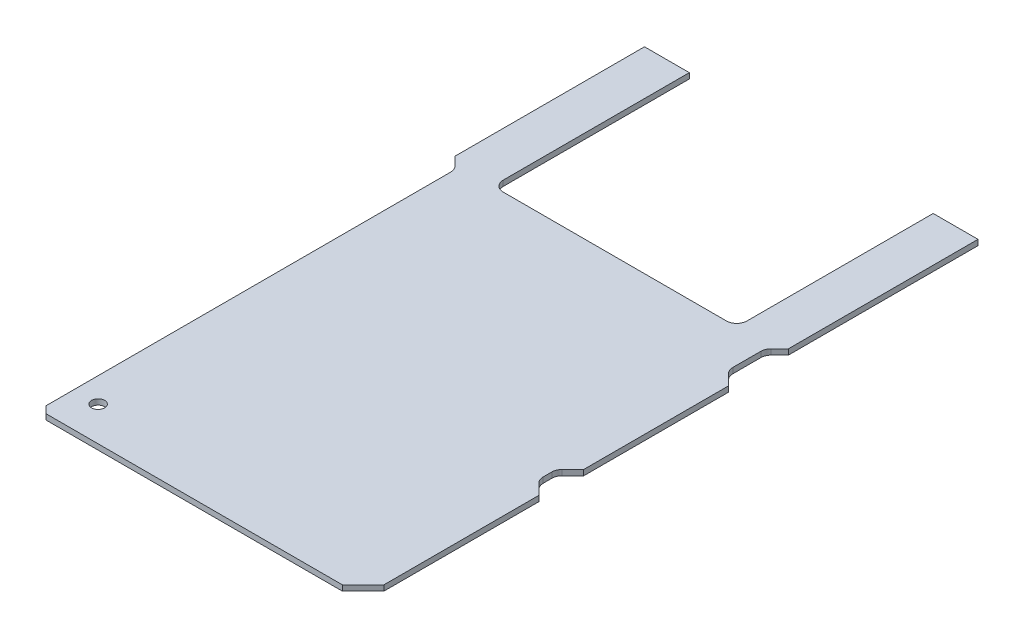
SolidWorks part; units mm, degrees
ref_plane "Front Plane" through (0, 0, 0) normal (0, 0, 1) x (1, 0, 0)
ref_plane "Top Plane" through (0, 0, 0) normal (0, 1, 0) x (1, 0, 0)
ref_plane "Right Plane" through (0, 0, 0) normal (1, 0, 0) x (0, 0, -1)
sketch "Sketch1" plane through (0, 0, 0) normal (0, 1, 0) x (1, 0, 0)
  line L1 (45, -88.5) -> (-45, -88.5)
  line L2 (45, -88.5) -> (45, 88.5)
  line L3 (45, 88.5) -> (-45, 88.5)
  line L4 (-45, -88.5) -> (-45, 88.5)
  line L5 (45, -88.5) -> (-45, 88.5) construction
  line L6 (45, 88.5) -> (-45, -88.5) construction
  point P0 (0, 0)
  dimension "D1" = 90
  dimension "D2" = 177
extrude "Boss-Extrude1" add sketch "Sketch1" along normal blind 1.6
sketch "Sketch5" plane through (0, 0, 0) normal (0, -1, 0) x (1, 0, 0)
  line L0 (45, 88.5) -> (45, -88.5) construction
  line L1 (37.6, -44) -> (37.6, -48)
  line L2 (37.6, -44) -> (22.4, -44)
  line L3 (22.4, -44) -> (22.4, -48)
  line L4 (37.6, -48) -> (22.4, -48)
  line L5 (16.1, -44) -> (16.1, -48)
  line L6 (16.1, -44) -> (0.9, -44)
  line L7 (0.9, -44) -> (0.9, -48)
  line L8 (16.1, -48) -> (0.9, -48)
  line L9 (37.6, -80) -> (37.6, -84)
  line L10 (37.6, -80) -> (22.4, -80)
  line L11 (22.4, -80) -> (22.4, -84)
  line L12 (37.6, -84) -> (22.4, -84)
  line L13 (12.1, -80) -> (12.1, -84)
  line L14 (12.1, -80) -> (-3.1, -80)
  line L15 (-3.1, -80) -> (-3.1, -84)
  line L16 (12.1, -84) -> (-3.1, -84)
  line L17 (2.025, -44.54) -> (14.975, -44.54)
  line L18 (2.025, -44.54) -> (2.025, -47.46)
  line L19 (2.025, -47.46) -> (14.975, -47.46)
  line L20 (14.975, -44.54) -> (14.975, -47.46)
  line L21 (23.525, -44.54) -> (36.475, -44.54)
  line L22 (23.525, -44.54) -> (23.525, -47.46)
  line L23 (23.525, -47.46) -> (36.475, -47.46)
  line L24 (36.475, -44.54) -> (36.475, -47.46)
  line L25 (-1.975, -80.54) -> (10.975, -80.54)
  line L26 (-1.975, -80.54) -> (-1.975, -83.46)
  line L27 (-1.975, -83.46) -> (10.975, -83.46)
  line L28 (10.975, -80.54) -> (10.975, -83.46)
  line L29 (23.525, -80.54) -> (36.475, -80.54)
  line L30 (23.525, -80.54) -> (23.525, -83.46)
  line L31 (23.525, -83.46) -> (36.475, -83.46)
  line L32 (36.475, -80.54) -> (36.475, -83.46)
  line L33 (-22, -41.5) -> (43, -41.5) construction
  line L34 (-22, -41.5) -> (-22, -86.5) construction
  line L35 (-22, -86.5) -> (43, -86.5) construction
  line L36 (43, -41.5) -> (43, -86.5) construction
  line L37 (45, -88.5) -> (-45, -88.5) construction
  point P16 (8.5, -44)
  point P17 (30, -44)
  point P18 (4.5, -84)
  point P19 (30, -84)
  point P25 (37.6, -82)
  point P26 (37.6, -46)
  point P38 (8.5, -44.54)
  point P39 (2.025, -46)
  point P40 (0.9, -46)
  point P41 (30, -44.54)
  point P42 (-1.975, -82)
  point P43 (-3.1, -82)
  point P44 (4.5, -83.46)
  point P45 (30, -83.46)
  dimension "D1" = 15.2
  dimension "D2" = 4
  dimension "D3" = 21.5
  dimension "D4" = 25.5
  dimension "D5" = 2.92
  dimension "D6" = 12.95
  dimension "D7" = 36
  dimension "D8" = 65
  dimension "D9" = 45
  dimension "D10" = 2.5
  dimension "D11" = 5.4
  dimension "D12" = 2
  dimension "D13" = 2
sketch "Sketch7" plane through (0, 0, 0) normal (0, -1, 0) x (1, 0, 0)
  line L0 (-45, -30.1257) -> (-48.3743, -33.5)
  line L1 (-45, -88.5) -> (-48.3743, -88.5)
  line L2 (-45, -88.5) -> (-45, -30.1257)
  line L4 (-48.3743, -88.5) -> (-48.3743, -33.5)
  line L5 (45, -88.5) -> (48.3743, -88.5)
  line L6 (45, -88.5) -> (45, -30.1257)
  line L8 (48.3743, -88.5) -> (48.3743, -33.5)
  line L9 (45, -30.1257) -> (48.3743, -33.5)
  line M9 (-45, 88.5) -> (-45, -88.5)
  line M11 (45, -88.5) -> (45, 88.5)
  dimension "D1" = 3.3743
  dimension "D2" = 55
  dimension "D3" = 45
extrude "Boss-Extrude4" add sketch "Sketch7" against normal up to surface (1.6 mm away) contours L4 L1 L0 M9 | L9 L5 L8 M11 region at (-46.6704, 0, -60.1481) region at (46.6704, 0, -60.1481) up to face at (0, 1.6, 0)
sketch "Sketch8" plane through (0, 1.6, 0) normal (0, 1, 0) x (1, 0, 0)
  line L0 (-30.48, 25.5) -> (30.48, 25.5) construction
  line L2 (48.3743, 88.5) -> (-48.3743, 88.5) construction
  line L3 (31.0783, -41.8002) -> (31.0783, -43.6252) construction
  line L4 (31.0783, -43.6252) -> (29.8783, -43.6252) construction
  line L5 (31.0783, -79.9002) -> (31.0783, -81.7252) construction
  line L6 (31.0783, -81.7252) -> (29.8783, -81.7252) construction
  line L7 (6.9977, -30.7614) -> (6.9977, -16.766)
  line L8 (6.9977, -16.766) -> (-6.9977, -16.766)
  line L9 (-6.9977, -16.766) -> (-6.9977, -30.7614)
  line L10 (-6.9977, -30.7614) -> (6.9977, -30.7614)
  line L11 (6.9977, -30.7614) -> (6.9977, -16.766)
  line L12 (6.9977, -16.766) -> (-6.9977, -16.766)
  line L13 (-6.9977, -16.766) -> (-6.9977, -30.7614)
  line L14 (-6.9977, -30.7614) -> (6.9977, -30.7614)
  line L15 (-11.9253, -30.7614) -> (-11.9253, -16.766)
  line L16 (-11.9253, -16.766) -> (-25.9207, -16.766)
  line L17 (-25.9207, -16.766) -> (-25.9207, -30.7614)
  line L18 (-25.9207, -30.7614) -> (-11.9253, -30.7614)
  line L19 (-11.9253, -30.7614) -> (-11.9253, -16.766)
  line L20 (-11.9253, -16.766) -> (-25.9207, -16.766)
  line L21 (-25.9207, -16.766) -> (-25.9207, -30.7614)
  line L22 (-25.9207, -30.7614) -> (-11.9253, -30.7614)
  line L23 (44.8437, -11.8384) -> (44.8437, 2.157)
  line L24 (44.8437, 2.157) -> (30.8483, 2.157)
  line L25 (30.8483, 2.157) -> (30.8483, -11.8384)
  line L26 (30.8483, -11.8384) -> (44.8437, -11.8384)
  line L27 (44.8437, -11.8384) -> (44.8437, 2.157)
  line L28 (44.8437, 2.157) -> (30.8483, 2.157)
  line L29 (30.8483, 2.157) -> (30.8483, -11.8384)
  line L30 (30.8483, -11.8384) -> (44.8437, -11.8384)
  line L31 (6.9977, -49.6844) -> (6.9977, -35.689)
  line L32 (6.9977, -35.689) -> (-6.9977, -35.689)
  line L33 (-6.9977, -35.689) -> (-6.9977, -49.6844)
  line L34 (-6.9977, -49.6844) -> (6.9977, -49.6844)
  line L35 (6.9977, -49.6844) -> (6.9977, -35.689)
  line L36 (6.9977, -35.689) -> (-6.9977, -35.689)
  line L37 (-6.9977, -35.689) -> (-6.9977, -49.6844)
  line L38 (-6.9977, -49.6844) -> (6.9977, -49.6844)
  line L39 (-11.9253, -49.6844) -> (-11.9253, -35.689)
  line L40 (-11.9253, -35.689) -> (-25.9207, -35.689)
  line L41 (-25.9207, -35.689) -> (-25.9207, -49.6844)
  line L42 (-25.9207, -49.6844) -> (-11.9253, -49.6844)
  line L43 (-11.9253, -49.6844) -> (-11.9253, -35.689)
  line L44 (-11.9253, -35.689) -> (-25.9207, -35.689)
  line L45 (-25.9207, -35.689) -> (-25.9207, -49.6844)
  line L46 (-25.9207, -49.6844) -> (-11.9253, -49.6844)
  line L47 (25.9207, -30.7614) -> (25.9207, -16.766)
  line L48 (25.9207, -16.766) -> (11.9253, -16.766)
  line L49 (11.9253, -16.766) -> (11.9253, -30.7614)
  line L50 (11.9253, -30.7614) -> (25.9207, -30.7614)
  line L51 (25.9207, -30.7614) -> (25.9207, -16.766)
  line L52 (25.9207, -16.766) -> (11.9253, -16.766)
  line L53 (11.9253, -16.766) -> (11.9253, -30.7614)
  line L54 (11.9253, -30.7614) -> (25.9207, -30.7614)
  line L55 (6.9977, -68.6074) -> (6.9977, -54.612)
  line L56 (6.9977, -54.612) -> (-6.9977, -54.612)
  line L57 (-6.9977, -54.612) -> (-6.9977, -68.6074)
  line L58 (-6.9977, -68.6074) -> (6.9977, -68.6074)
  line L59 (6.9977, -68.6074) -> (6.9977, -54.612)
  line L60 (6.9977, -54.612) -> (-6.9977, -54.612)
  line L61 (-6.9977, -54.612) -> (-6.9977, -68.6074)
  line L62 (-6.9977, -68.6074) -> (6.9977, -68.6074)
  line L63 (-11.9253, -68.6074) -> (-11.9253, -54.612)
  line L64 (-11.9253, -54.612) -> (-25.9207, -54.612)
  line L65 (-25.9207, -54.612) -> (-25.9207, -68.6074)
  line L66 (-25.9207, -68.6074) -> (-11.9253, -68.6074)
  line L67 (-11.9253, -68.6074) -> (-11.9253, -54.612)
  line L68 (-11.9253, -54.612) -> (-25.9207, -54.612)
  line L69 (-25.9207, -54.612) -> (-25.9207, -68.6074)
  line L70 (-25.9207, -68.6074) -> (-11.9253, -68.6074)
  line L71 (25.9207, -49.6844) -> (25.9207, -35.689)
  line L72 (25.9207, -35.689) -> (11.9253, -35.689)
  line L73 (11.9253, -35.689) -> (11.9253, -49.6844)
  line L74 (11.9253, -49.6844) -> (25.9207, -49.6844)
  line L75 (25.9207, -49.6844) -> (25.9207, -35.689)
  line L76 (25.9207, -35.689) -> (11.9253, -35.689)
  line L77 (11.9253, -35.689) -> (11.9253, -49.6844)
  line L78 (11.9253, -49.6844) -> (25.9207, -49.6844)
  line L79 (25.9207, -68.6074) -> (25.9207, -54.612)
  line L80 (25.9207, -54.612) -> (11.9253, -54.612)
  line L81 (11.9253, -54.612) -> (11.9253, -68.6074)
  line L82 (11.9253, -68.6074) -> (25.9207, -68.6074)
  line L83 (25.9207, -68.6074) -> (25.9207, -54.612)
  line L84 (25.9207, -54.612) -> (11.9253, -54.612)
  line L85 (11.9253, -54.612) -> (11.9253, -68.6074)
  line L86 (11.9253, -68.6074) -> (25.9207, -68.6074)
  line L87 (-30.8483, -30.7614) -> (-30.8483, -16.766)
  line L88 (-30.8483, -16.766) -> (-44.8437, -16.766)
  line L89 (-44.8437, -16.766) -> (-44.8437, -30.7614)
  line L90 (-44.8437, -30.7614) -> (-30.8483, -30.7614)
  line L91 (-30.8483, -30.7614) -> (-30.8483, -16.766)
  line L92 (-30.8483, -16.766) -> (-44.8437, -16.766)
  line L93 (-44.8437, -16.766) -> (-44.8437, -30.7614)
  line L94 (-44.8437, -30.7614) -> (-30.8483, -30.7614)
  line L95 (-30.8483, -11.8384) -> (-30.8483, 2.157)
  line L96 (-30.8483, 2.157) -> (-44.8437, 2.157)
  line L97 (-44.8437, 2.157) -> (-44.8437, -11.8384)
  line L98 (-44.8437, -11.8384) -> (-30.8483, -11.8384)
  line L99 (-30.8483, -11.8384) -> (-30.8483, 2.157)
  line L100 (-30.8483, 2.157) -> (-44.8437, 2.157)
  line L101 (-44.8437, 2.157) -> (-44.8437, -11.8384)
  line L102 (-44.8437, -11.8384) -> (-30.8483, -11.8384)
  line L103 (25.9207, -87.5304) -> (25.9207, -73.535)
  line L104 (25.9207, -73.535) -> (11.9253, -73.535)
  line L105 (11.9253, -73.535) -> (11.9253, -87.5304)
  line L106 (11.9253, -87.5304) -> (25.9207, -87.5304)
  line L107 (25.9207, -87.5304) -> (25.9207, -73.535)
  line L108 (25.9207, -73.535) -> (11.9253, -73.535)
  line L109 (11.9253, -73.535) -> (11.9253, -87.5304)
  line L110 (11.9253, -87.5304) -> (25.9207, -87.5304)
  line L111 (-30.8483, -87.5304) -> (-30.8483, -73.535)
  line L112 (-30.8483, -73.535) -> (-44.8437, -73.535)
  line L113 (-44.8437, -73.535) -> (-44.8437, -87.5304)
  line L114 (-44.8437, -87.5304) -> (-30.8483, -87.5304)
  line L115 (-30.8483, -87.5304) -> (-30.8483, -73.535)
  line L116 (-30.8483, -73.535) -> (-44.8437, -73.535)
  line L117 (-44.8437, -73.535) -> (-44.8437, -87.5304)
  line L118 (-44.8437, -87.5304) -> (-30.8483, -87.5304)
  line L119 (-30.8483, -68.6074) -> (-30.8483, -54.612)
  line L120 (-30.8483, -54.612) -> (-44.8437, -54.612)
  line L121 (-44.8437, -54.612) -> (-44.8437, -68.6074)
  line L122 (-44.8437, -68.6074) -> (-30.8483, -68.6074)
  line L123 (-30.8483, -68.6074) -> (-30.8483, -54.612)
  line L124 (-30.8483, -54.612) -> (-44.8437, -54.612)
  line L125 (-44.8437, -54.612) -> (-44.8437, -68.6074)
  line L126 (-44.8437, -68.6074) -> (-30.8483, -68.6074)
  line L127 (-30.8483, -49.6844) -> (-30.8483, -35.689)
  line L128 (-30.8483, -35.689) -> (-44.8437, -35.689)
  line L129 (-44.8437, -35.689) -> (-44.8437, -49.6844)
  line L130 (-44.8437, -49.6844) -> (-30.8483, -49.6844)
  line L131 (-30.8483, -49.6844) -> (-30.8483, -35.689)
  line L132 (-30.8483, -35.689) -> (-44.8437, -35.689)
  line L133 (-44.8437, -35.689) -> (-44.8437, -49.6844)
  line L134 (-44.8437, -49.6844) -> (-30.8483, -49.6844)
  line L135 (45.0596, 90.786) -> (-45.0596, 90.786)
  line L136 (-45.0596, 90.786) -> (-45.0596, 30.08)
  line L137 (-45.0596, 30.08) -> (45.0596, 30.08)
  line L138 (45.0596, 30.08) -> (45.0596, 90.786)
  line L139 (45.0596, 90.786) -> (-45.0596, 90.786)
  line L140 (-45.0596, 90.786) -> (-45.0596, 30.08)
  line L141 (-45.0596, 30.08) -> (45.0596, 30.08)
  line L142 (45.0596, 30.08) -> (45.0596, 90.786)
  line L143 (52.5, 98.836) -> (-52.5, 98.836)
  line L144 (52.5, -93.5094) -> (52.5, 98.836)
  line L145 (-52.5, -93.5094) -> (52.5, -93.5094)
  line L146 (-52.5, 98.836) -> (-52.5, -93.5094)
  line L147 (52.5, 98.836) -> (-52.5, 98.836)
  line L148 (52.5, -93.5094) -> (52.5, 98.836)
  line L149 (-52.5, -93.5094) -> (52.5, -93.5094)
  line L150 (-52.5, 98.836) -> (-52.5, -93.5094)
  line L151 (-18.0365, -73.765) -> (-19.8615, -73.765) construction
  line L152 (-19.8615, -73.765) -> (-19.8615, -72.565) construction
  line L153 (31.8783, -41.8002) -> (31.0783, -41.8002) construction
  line L154 (31.8783, -79.9002) -> (31.0783, -79.9002) construction
  line L155 (-18.0365, -74.565) -> (-18.0365, -73.765) construction
  line L156 (31.8783, -40.2252) -> (31.8783, -41.8002) construction
  line L157 (31.8783, -78.3252) -> (31.8783, -79.9002) construction
  line L158 (-16.4615, -74.565) -> (-18.0365, -74.565) construction
  line L159 (-6.9977, 7.0846) -> (-6.9977, 21.08) construction
  line L160 (6.9977, 21.08) -> (-6.9977, 21.08) construction
  line L161 (31.0783, -48.4502) -> (37.3483, -48.4502) construction
  line L162 (37.3483, -48.4502) -> (40.1483, -48.4502) construction
  line L163 (31.0783, -86.5502) -> (37.3483, -86.5502) construction
  line L164 (37.3483, -86.5502) -> (40.1483, -86.5502) construction
  line L165 (-24.6865, -73.765) -> (-24.6865, -80.035) construction
  line L166 (-24.6865, -80.035) -> (-24.6865, -82.835) construction
  line L167 (6.9977, 7.0846) -> (-6.9977, 7.0846) construction
  line L168 (43.3783, -48.4502) -> (43.3783, -41.8002) construction
  line L169 (43.3783, -41.8002) -> (42.5783, -41.8002) construction
  line L170 (43.3783, -86.5502) -> (43.3783, -79.9002) construction
  line L171 (43.3783, -79.9002) -> (42.5783, -79.9002) construction
  line L172 (-24.6865, -86.065) -> (-18.0365, -86.065) construction
  line L173 (-18.0365, -86.065) -> (-18.0365, -85.265) construction
  line L174 (6.9977, 7.0846) -> (6.9977, 21.08) construction
  line L175 (40.1483, -48.4502) -> (43.3783, -48.4502) construction
  line L176 (40.1483, -86.5502) -> (43.3783, -86.5502) construction
  line L177 (-24.6865, -82.835) -> (-24.6865, -86.065) construction
  line L178 (-25.9207, 7.0846) -> (-25.9207, 21.08) construction
  line L179 (-11.9253, 21.08) -> (-25.9207, 21.08) construction
  line L180 (29.8783, -43.6252) -> (29.8783, -46.6252) construction
  line L181 (29.8783, -81.7252) -> (29.8783, -84.7252) construction
  line L182 (-19.8615, -72.565) -> (-22.8615, -72.565) construction
  line L183 (-11.9253, 7.0846) -> (-25.9207, 7.0846) construction
  line L184 (31.0783, -46.6252) -> (31.0783, -48.4502) construction
  line L185 (31.0783, -84.7252) -> (31.0783, -86.5502) construction
  line L186 (-22.8615, -73.765) -> (-24.6865, -73.765) construction
  line L187 (-30.8483, 7.0846) -> (-44.8437, 7.0846) construction
  line L188 (-30.8483, 7.0846) -> (-30.8483, 21.08) construction
  line L189 (-30.8483, 21.08) -> (-44.8437, 21.08) construction
  line L190 (-44.8437, 7.0846) -> (-44.8437, 21.08) construction
  line L191 (30.8483, -26.2252) -> (30.8483, -40.2252) construction
  line L192 (30.8483, -40.2252) -> (31.8783, -40.2252) construction
  line L193 (30.8483, -64.3252) -> (30.8483, -78.3252) construction
  line L194 (30.8483, -78.3252) -> (31.8783, -78.3252) construction
  line L195 (-2.4615, -73.535) -> (-16.4615, -73.535) construction
  line L196 (-16.4615, -73.535) -> (-16.4615, -74.565) construction
  line L197 (-11.9253, 7.0846) -> (-11.9253, 21.08) construction
  line L198 (29.8783, -46.6252) -> (31.0783, -46.6252) construction
  line L199 (29.8783, -84.7252) -> (31.0783, -84.7252) construction
  line L200 (-22.8615, -72.565) -> (-22.8615, -73.765) construction
  line L201 (-6.9977, -11.8384) -> (-6.9977, 2.157) construction
  line L202 (6.9977, 2.157) -> (-6.9977, 2.157) construction
  line L203 (31.0783, -19.8252) -> (31.0783, -18.0002) construction
  line L204 (29.8783, -19.8252) -> (31.0783, -19.8252) construction
  line L205 (31.0783, -57.9252) -> (31.0783, -56.1002) construction
  line L206 (29.8783, -57.9252) -> (31.0783, -57.9252) construction
  line L207 (3.9385, -73.765) -> (5.7635, -73.765) construction
  line L208 (3.9385, -72.565) -> (3.9385, -73.765) construction
  line L209 (6.9977, -11.8384) -> (-6.9977, -11.8384) construction
  line L210 (31.0783, -22.8252) -> (29.8783, -22.8252) construction
  line L211 (31.0783, -24.6502) -> (31.0783, -22.8252) construction
  line L212 (31.0783, -60.9252) -> (29.8783, -60.9252) construction
  line L213 (31.0783, -62.7502) -> (31.0783, -60.9252) construction
  line L214 (0.9385, -73.765) -> (0.9385, -72.565) construction
  line L215 (-0.8865, -73.765) -> (0.9385, -73.765) construction
  line L216 (6.9977, -11.8384) -> (6.9977, 2.157) construction
  line L217 (29.8783, -22.8252) -> (29.8783, -19.8252) construction
  line L218 (29.8783, -60.9252) -> (29.8783, -57.9252) construction
  line L219 (0.9385, -72.565) -> (3.9385, -72.565) construction
  line L220 (-25.9207, -11.8384) -> (-25.9207, 2.157) construction
  line L221 (-11.9253, 2.157) -> (-25.9207, 2.157) construction
  line L222 (43.3783, -18.0002) -> (43.3783, -24.6502) construction
  line L223 (40.1483, -18.0002) -> (43.3783, -18.0002) construction
  line L224 (43.3783, -56.1002) -> (43.3783, -62.7502) construction
  line L225 (40.1483, -56.1002) -> (43.3783, -56.1002) construction
  line L226 (5.7635, -86.065) -> (-0.8865, -86.065) construction
  line L227 (5.7635, -82.835) -> (5.7635, -86.065) construction
  line L228 (-11.9253, -11.8384) -> (-25.9207, -11.8384) construction
  line L229 (31.0783, -18.0002) -> (37.3483, -18.0002) construction
  line L230 (31.0783, -56.1002) -> (37.3483, -56.1002) construction
  line L231 (5.7635, -73.765) -> (5.7635, -80.035) construction
  line L232 (-11.9253, -11.8384) -> (-11.9253, 2.157) construction
  line L233 (37.3483, -18.0002) -> (40.1483, -18.0002) construction
  line L234 (37.3483, -56.1002) -> (40.1483, -56.1002) construction
  line L235 (5.7635, -80.035) -> (5.7635, -82.835) construction
  line L236 (30.8483, 7.0846) -> (30.8483, 21.08) construction
  line L237 (44.8437, 21.08) -> (30.8483, 21.08) construction
  line L238 (44.8483, -40.2252) -> (44.8483, -26.2252) construction
  line L239 (42.5783, -26.2252) -> (44.8483, -26.2252) construction
  line L240 (44.8483, -78.3252) -> (44.8483, -64.3252) construction
  line L241 (42.5783, -64.3252) -> (44.8483, -64.3252) construction
  line L242 (-16.4615, -87.535) -> (-2.4615, -87.535) construction
  line L243 (-2.4615, -85.265) -> (-2.4615, -87.535) construction
  line L244 (44.8437, 7.0846) -> (30.8483, 7.0846) construction
  line L245 (43.3783, -24.6502) -> (42.5783, -24.6502) construction
  line L246 (43.3783, -62.7502) -> (42.5783, -62.7502) construction
  line L247 (-0.8865, -86.065) -> (-0.8865, -85.265) construction
  line L248 (44.8437, 7.0846) -> (44.8437, 21.08) construction
  line L249 (42.5783, -24.6502) -> (42.5783, -26.2252) construction
  line L250 (42.5783, -62.7502) -> (42.5783, -64.3252) construction
  line L251 (-0.8865, -85.265) -> (-2.4615, -85.265) construction
  line L252 (25.9207, 7.0846) -> (11.9253, 7.0846) construction
  line L253 (11.9253, 7.0846) -> (11.9253, 21.08) construction
  line L254 (25.9207, 21.08) -> (11.9253, 21.08) construction
  line L255 (42.5783, -41.8002) -> (42.5783, -40.2252) construction
  line L256 (42.5783, -79.9002) -> (42.5783, -78.3252) construction
  line L257 (-18.0365, -85.265) -> (-16.4615, -85.265) construction
  line L258 (25.9207, 7.0846) -> (25.9207, 21.08) construction
  line L259 (42.5783, -40.2252) -> (44.8483, -40.2252) construction
  line L260 (42.5783, -78.3252) -> (44.8483, -78.3252) construction
  line L261 (-16.4615, -85.265) -> (-16.4615, -87.535) construction
  line L262 (11.9253, -11.8384) -> (11.9253, 2.157) construction
  line L263 (25.9207, 2.157) -> (11.9253, 2.157) construction
  line L264 (31.8783, -24.6502) -> (31.0783, -24.6502) construction
  line L265 (31.8783, -62.7502) -> (31.0783, -62.7502) construction
  line L266 (-0.8865, -74.565) -> (-0.8865, -73.765) construction
  line L267 (25.9207, -11.8384) -> (11.9253, -11.8384) construction
  line L268 (30.8483, -26.2252) -> (31.8783, -26.2252) construction
  line L269 (30.8483, -64.3252) -> (31.8783, -64.3252) construction
  line L270 (-2.4615, -73.535) -> (-2.4615, -74.565) construction
  line L271 (25.9207, -11.8384) -> (25.9207, 2.157) construction
  line L272 (31.8783, -26.2252) -> (31.8783, -24.6502) construction
  line L273 (31.8783, -64.3252) -> (31.8783, -62.7502) construction
  line L274 (-2.4615, -74.565) -> (-0.8865, -74.565) construction
  line L275 (-24.6865, -86.065) -> (-25.1945, -86.065) construction
  line L276 (-25.1945, -86.065) -> (-25.1945, -73.765) construction
  line L277 (-25.1945, -73.765) -> (-24.6865, -73.765) construction
  line L278 (31.0783, -48.4502) -> (31.0783, -48.9582) construction
  line L279 (31.0783, -48.9582) -> (43.3783, -48.9582) construction
  line L280 (43.3783, -48.9582) -> (43.3783, -48.4502) construction
  line L281 (31.0783, -56.1002) -> (31.0783, -55.5922) construction
  line L282 (31.0783, -55.5922) -> (43.3783, -55.5922) construction
  line L283 (43.3783, -55.5922) -> (43.3783, -56.1002) construction
  line L284 (31.0783, -86.5502) -> (31.0783, -87.0582) construction
  line L285 (31.0783, -87.0582) -> (43.3783, -87.0582) construction
  line L286 (43.3783, -87.0582) -> (43.3783, -86.5502) construction
  line L287 (5.7635, -73.765) -> (6.2715, -73.765) construction
  line L288 (6.2715, -73.765) -> (6.2715, -86.065) construction
  line L289 (6.2715, -86.065) -> (5.7635, -86.065) construction
  line L290 (31.0783, -18.0002) -> (31.0783, -17.4922) construction
  line L291 (31.0783, -17.4922) -> (43.3783, -17.4922) construction
  line L292 (43.3783, -17.4922) -> (43.3783, -18.0002) construction
  line L293 (31.0783, -41.8002) -> (31.0783, -43.6252)
  line L294 (31.0783, -43.6252) -> (29.8783, -43.6252)
  line L295 (31.0783, -79.9002) -> (31.0783, -81.7252)
  line L296 (31.0783, -81.7252) -> (29.8783, -81.7252)
  line L297 (-18.0365, -73.765) -> (-19.8615, -73.765)
  line L298 (-19.8615, -73.765) -> (-19.8615, -72.565)
  line L299 (31.8783, -41.8002) -> (31.0783, -41.8002)
  line L300 (31.8783, -79.9002) -> (31.0783, -79.9002)
  line L301 (-18.0365, -74.565) -> (-18.0365, -73.765)
  line L302 (31.8783, -40.2252) -> (31.8783, -41.8002)
  line L303 (31.8783, -78.3252) -> (31.8783, -79.9002)
  line L304 (-16.4615, -74.565) -> (-18.0365, -74.565)
  line L305 (-6.9977, 7.0846) -> (-6.9977, 21.08)
  line L306 (6.9977, 21.08) -> (-6.9977, 21.08)
  line L307 (31.0783, -48.4502) -> (37.3483, -48.4502)
  line L308 (37.3483, -48.4502) -> (40.1483, -48.4502)
  line L309 (31.0783, -86.5502) -> (37.3483, -86.5502)
  line L310 (37.3483, -86.5502) -> (40.1483, -86.5502)
  line L311 (-24.6865, -73.765) -> (-24.6865, -80.035)
  line L312 (-24.6865, -80.035) -> (-24.6865, -82.835)
  line L313 (6.9977, 7.0846) -> (-6.9977, 7.0846)
  line L314 (43.3783, -48.4502) -> (43.3783, -41.8002)
  line L315 (43.3783, -41.8002) -> (42.5783, -41.8002)
  line L316 (43.3783, -86.5502) -> (43.3783, -79.9002)
  line L317 (43.3783, -79.9002) -> (42.5783, -79.9002)
  line L318 (-24.6865, -86.065) -> (-18.0365, -86.065)
  line L319 (-18.0365, -86.065) -> (-18.0365, -85.265)
  line L320 (6.9977, 7.0846) -> (6.9977, 21.08)
  line L321 (40.1483, -48.4502) -> (43.3783, -48.4502)
  line L322 (40.1483, -86.5502) -> (43.3783, -86.5502)
  line L323 (-24.6865, -82.835) -> (-24.6865, -86.065)
  line L324 (-25.9207, 7.0846) -> (-25.9207, 21.08)
  line L325 (-11.9253, 21.08) -> (-25.9207, 21.08)
  line L326 (29.8783, -43.6252) -> (29.8783, -46.6252)
  line L327 (29.8783, -81.7252) -> (29.8783, -84.7252)
  line L328 (-19.8615, -72.565) -> (-22.8615, -72.565)
  line L329 (-11.9253, 7.0846) -> (-25.9207, 7.0846)
  line L330 (31.0783, -46.6252) -> (31.0783, -48.4502)
  line L331 (31.0783, -84.7252) -> (31.0783, -86.5502)
  line L332 (-22.8615, -73.765) -> (-24.6865, -73.765)
  line L333 (-30.8483, 7.0846) -> (-44.8437, 7.0846)
  line L334 (-30.8483, 7.0846) -> (-30.8483, 21.08)
  line L335 (-30.8483, 21.08) -> (-44.8437, 21.08)
  line L336 (-44.8437, 7.0846) -> (-44.8437, 21.08)
  line L337 (30.8483, -26.2252) -> (30.8483, -40.2252)
  line L338 (30.8483, -40.2252) -> (31.8783, -40.2252)
  line L339 (30.8483, -64.3252) -> (30.8483, -78.3252)
  line L340 (30.8483, -78.3252) -> (31.8783, -78.3252)
  line L341 (-2.4615, -73.535) -> (-16.4615, -73.535)
  line L342 (-16.4615, -73.535) -> (-16.4615, -74.565)
  line L343 (-11.9253, 7.0846) -> (-11.9253, 21.08)
  line L344 (29.8783, -46.6252) -> (31.0783, -46.6252)
  line L345 (29.8783, -84.7252) -> (31.0783, -84.7252)
  line L346 (-22.8615, -72.565) -> (-22.8615, -73.765)
  line L347 (-6.9977, -11.8384) -> (-6.9977, 2.157)
  line L348 (6.9977, 2.157) -> (-6.9977, 2.157)
  line L349 (31.0783, -19.8252) -> (31.0783, -18.0002)
  line L350 (29.8783, -19.8252) -> (31.0783, -19.8252)
  line L351 (31.0783, -57.9252) -> (31.0783, -56.1002)
  line L352 (29.8783, -57.9252) -> (31.0783, -57.9252)
  line L353 (3.9385, -73.765) -> (5.7635, -73.765)
  line L354 (3.9385, -72.565) -> (3.9385, -73.765)
  line L355 (6.9977, -11.8384) -> (-6.9977, -11.8384)
  line L356 (31.0783, -22.8252) -> (29.8783, -22.8252)
  line L357 (31.0783, -24.6502) -> (31.0783, -22.8252)
  line L358 (31.0783, -60.9252) -> (29.8783, -60.9252)
  line L359 (31.0783, -62.7502) -> (31.0783, -60.9252)
  line L360 (0.9385, -73.765) -> (0.9385, -72.565)
  line L361 (-0.8865, -73.765) -> (0.9385, -73.765)
  line L362 (6.9977, -11.8384) -> (6.9977, 2.157)
  line L363 (29.8783, -22.8252) -> (29.8783, -19.8252)
  line L364 (29.8783, -60.9252) -> (29.8783, -57.9252)
  line L365 (0.9385, -72.565) -> (3.9385, -72.565)
  line L366 (-25.9207, -11.8384) -> (-25.9207, 2.157)
  line L367 (-11.9253, 2.157) -> (-25.9207, 2.157)
  line L368 (43.3783, -18.0002) -> (43.3783, -24.6502)
  line L369 (40.1483, -18.0002) -> (43.3783, -18.0002)
  line L370 (43.3783, -56.1002) -> (43.3783, -62.7502)
  line L371 (40.1483, -56.1002) -> (43.3783, -56.1002)
  line L372 (5.7635, -86.065) -> (-0.8865, -86.065)
  line L373 (5.7635, -82.835) -> (5.7635, -86.065)
  line L374 (-11.9253, -11.8384) -> (-25.9207, -11.8384)
  line L375 (31.0783, -18.0002) -> (37.3483, -18.0002)
  line L376 (31.0783, -56.1002) -> (37.3483, -56.1002)
  line L377 (5.7635, -73.765) -> (5.7635, -80.035)
  line L378 (-11.9253, -11.8384) -> (-11.9253, 2.157)
  line L379 (37.3483, -18.0002) -> (40.1483, -18.0002)
  line L380 (37.3483, -56.1002) -> (40.1483, -56.1002)
  line L381 (5.7635, -80.035) -> (5.7635, -82.835)
  line L382 (30.8483, 7.0846) -> (30.8483, 21.08)
  line L383 (44.8437, 21.08) -> (30.8483, 21.08)
  line L384 (44.8483, -40.2252) -> (44.8483, -26.2252)
  line L385 (42.5783, -26.2252) -> (44.8483, -26.2252)
  line L386 (44.8483, -78.3252) -> (44.8483, -64.3252)
  line L387 (42.5783, -64.3252) -> (44.8483, -64.3252)
  line L388 (-16.4615, -87.535) -> (-2.4615, -87.535)
  line L389 (-2.4615, -85.265) -> (-2.4615, -87.535)
  line L390 (44.8437, 7.0846) -> (30.8483, 7.0846)
  line L391 (43.3783, -24.6502) -> (42.5783, -24.6502)
  line L392 (43.3783, -62.7502) -> (42.5783, -62.7502)
  line L393 (-0.8865, -86.065) -> (-0.8865, -85.265)
  line L394 (44.8437, 7.0846) -> (44.8437, 21.08)
  line L395 (42.5783, -24.6502) -> (42.5783, -26.2252)
  line L396 (42.5783, -62.7502) -> (42.5783, -64.3252)
  line L397 (-0.8865, -85.265) -> (-2.4615, -85.265)
  line L398 (25.9207, 7.0846) -> (11.9253, 7.0846)
  line L399 (11.9253, 7.0846) -> (11.9253, 21.08)
  line L400 (25.9207, 21.08) -> (11.9253, 21.08)
  line L401 (42.5783, -41.8002) -> (42.5783, -40.2252)
  line L402 (42.5783, -79.9002) -> (42.5783, -78.3252)
  line L403 (-18.0365, -85.265) -> (-16.4615, -85.265)
  line L404 (25.9207, 7.0846) -> (25.9207, 21.08)
  line L405 (42.5783, -40.2252) -> (44.8483, -40.2252)
  line L406 (42.5783, -78.3252) -> (44.8483, -78.3252)
  line L407 (-16.4615, -85.265) -> (-16.4615, -87.535)
  line L408 (11.9253, -11.8384) -> (11.9253, 2.157)
  line L409 (25.9207, 2.157) -> (11.9253, 2.157)
  line L410 (31.8783, -24.6502) -> (31.0783, -24.6502)
  line L411 (31.8783, -62.7502) -> (31.0783, -62.7502)
  line L412 (-0.8865, -74.565) -> (-0.8865, -73.765)
  line L413 (25.9207, -11.8384) -> (11.9253, -11.8384)
  line L414 (30.8483, -26.2252) -> (31.8783, -26.2252)
  line L415 (30.8483, -64.3252) -> (31.8783, -64.3252)
  line L416 (-2.4615, -73.535) -> (-2.4615, -74.565)
  line L417 (25.9207, -11.8384) -> (25.9207, 2.157)
  line L418 (31.8783, -26.2252) -> (31.8783, -24.6502)
  line L419 (31.8783, -64.3252) -> (31.8783, -62.7502)
  line L420 (-2.4615, -74.565) -> (-0.8865, -74.565)
  line L421 (-24.6865, -86.065) -> (-25.1945, -86.065)
  line L422 (-25.1945, -86.065) -> (-25.1945, -73.765)
  line L423 (-25.1945, -73.765) -> (-24.6865, -73.765)
  line L424 (31.0783, -48.4502) -> (31.0783, -48.9582)
  line L425 (31.0783, -48.9582) -> (43.3783, -48.9582)
  line L426 (43.3783, -48.9582) -> (43.3783, -48.4502)
  line L427 (31.0783, -56.1002) -> (31.0783, -55.5922)
  line L428 (31.0783, -55.5922) -> (43.3783, -55.5922)
  line L429 (43.3783, -55.5922) -> (43.3783, -56.1002)
  line L430 (31.0783, -86.5502) -> (31.0783, -87.0582)
  line L431 (31.0783, -87.0582) -> (43.3783, -87.0582)
  line L432 (43.3783, -87.0582) -> (43.3783, -86.5502)
  line L433 (5.7635, -73.765) -> (6.2715, -73.765)
  line L434 (6.2715, -73.765) -> (6.2715, -86.065)
  line L435 (6.2715, -86.065) -> (5.7635, -86.065)
  line L436 (31.0783, -18.0002) -> (31.0783, -17.4922)
  line L437 (31.0783, -17.4922) -> (43.3783, -17.4922)
  line L438 (43.3783, -17.4922) -> (43.3783, -18.0002)
  circle A0 centre (-45.8343, 84.563) radius 0.4318 construction
  circle A1 centre (-45.8343, 84.563) radius 0.4318
  circle A2 centre (45.8343, 84.563) radius 0.4318 construction
  circle A3 centre (45.8343, 84.563) radius 0.4318
  circle A8 centre (-45.8343, 82.023) radius 0.4318
  circle A9 centre (45.8343, 82.023) radius 0.4318
  circle A10 centre (-45.8343, 79.483) radius 0.4318
  circle A11 centre (45.8343, 79.483) radius 0.4318
  circle A12 centre (-45.8343, 76.943) radius 0.4318
  circle A13 centre (45.8343, 76.943) radius 0.4318
  circle A14 centre (-45.8343, 74.403) radius 0.4318
  circle A15 centre (45.8343, 74.403) radius 0.4318
  circle A16 centre (-45.8343, 71.863) radius 0.4318
  circle A17 centre (45.8343, 71.863) radius 0.4318
  circle A18 centre (-45.8343, 69.323) radius 0.4318
  circle A19 centre (45.8343, 69.323) radius 0.4318
  circle A20 centre (-45.8343, 66.783) radius 0.4318
  circle A21 centre (45.8343, 66.783) radius 0.4318
  circle A22 centre (-45.8343, 64.243) radius 0.4318
  circle A23 centre (45.8343, 64.243) radius 0.4318
  circle A24 centre (-45.8343, 61.703) radius 0.4318
  circle A25 centre (45.8343, 61.703) radius 0.4318
  circle A26 centre (-45.8343, 59.163) radius 0.4318
  circle A27 centre (45.8343, 59.163) radius 0.4318
  circle A28 centre (-45.8343, 56.623) radius 0.4318
  circle A29 centre (45.8343, 56.623) radius 0.4318
  circle A30 centre (-45.8343, 54.083) radius 0.4318
  circle A31 centre (45.8343, 54.083) radius 0.4318
  circle A32 centre (-45.8343, 51.543) radius 0.4318
  circle A33 centre (45.8343, 51.543) radius 0.4318
  circle A34 centre (-45.8343, 49.003) radius 0.4318
  circle A35 centre (45.8343, 49.003) radius 0.4318
  circle A36 centre (-45.8343, 46.463) radius 0.4318
  circle A37 centre (45.8343, 46.463) radius 0.4318
  circle A38 centre (-45.8343, 43.923) radius 0.4318
  circle A39 centre (45.8343, 43.923) radius 0.4318
  circle A40 centre (-45.8343, 41.383) radius 0.4318
  circle A41 centre (45.8343, 41.383) radius 0.4318
  circle A42 centre (-45.8343, 38.843) radius 0.4318
  circle A43 centre (45.8343, 38.843) radius 0.4318
  circle A44 centre (-45.8343, 36.303) radius 0.4318
  circle A45 centre (45.8343, 36.303) radius 0.4318
  arc A47 (-45.0596, 32.62) -> (-42.5196, 30.08) centre (-42.5196, 32.62) ccw construction
  circle A48 centre (-37.846, -80.5327) radius 1.9
  circle A49 centre (-30.48, 25.5) radius 0.4318
  circle A50 centre (-27.94, 25.5) radius 0.4318
  circle A51 centre (-25.4, 25.5) radius 0.4318
  circle A52 centre (-22.86, 25.5) radius 0.4318
  circle A53 centre (-20.32, 25.5) radius 0.4318
  circle A54 centre (-17.78, 25.5) radius 0.4318
  circle A55 centre (-15.24, 25.5) radius 0.4318
  circle A56 centre (-12.7, 25.5) radius 0.4318
  circle A57 centre (-10.16, 25.5) radius 0.4318
  circle A58 centre (-7.62, 25.5) radius 0.4318
  circle A59 centre (-5.08, 25.5) radius 0.4318
  circle A60 centre (-2.54, 25.5) radius 0.4318
  circle A61 centre (0, 25.5) radius 0.4318
  circle A62 centre (2.54, 25.5) radius 0.4318
  circle A63 centre (5.08, 25.5) radius 0.4318
  circle A64 centre (7.62, 25.5) radius 0.4318
  circle A65 centre (10.16, 25.5) radius 0.4318
  circle A66 centre (12.7, 25.5) radius 0.4318
  circle A67 centre (15.24, 25.5) radius 0.4318
  circle A68 centre (17.78, 25.5) radius 0.4318
  circle A69 centre (20.32, 25.5) radius 0.4318
  circle A70 centre (22.86, 25.5) radius 0.4318
  circle A71 centre (25.4, 25.5) radius 0.4318
  circle A72 centre (27.94, 25.5) radius 0.4318
  circle A73 centre (30.48, 25.5) radius 0.4318
  circle A74 centre (-37.846, -80.5327) radius 2
  circle A75 centre (-37.846, -80.5327) radius 2
  arc A76 (42.5196, 30.08) -> (45.0596, 32.62) centre (42.5196, 32.62) ccw construction
  arc A77 (45.0596, 88.246) -> (42.5196, 90.786) centre (42.5196, 88.246) ccw construction
  arc A78 (-42.5196, 90.786) -> (-45.0596, 88.246) centre (-42.5196, 88.246) ccw construction
  arc A79 (-45.0596, 32.62) -> (-42.5196, 30.08) centre (-42.5196, 32.62) ccw
  arc A80 (42.5196, 30.08) -> (45.0596, 32.62) centre (42.5196, 32.62) ccw
  arc A81 (45.0596, 88.246) -> (42.5196, 90.786) centre (42.5196, 88.246) ccw
  arc A82 (-42.5196, 90.786) -> (-45.0596, 88.246) centre (-42.5196, 88.246) ccw
  dimension "D3" = 3.8
  dimension "D2" = 2.54
  dimension "D5" = 2.54
  dimension "D6" = 63
  dimension "D1" = 20
  dimension "D7" = 0
  dimension "D8" = 0
  dimension "D9" = 0
  dimension "D10" = 0
  dimension "D11" = 0
  dimension "D12" = 0
  dimension "D13" = 0
  dimension "D14" = 0
  dimension "D15" = 0
  dimension "D16" = 0
  dimension "D17" = 0
  dimension "D18" = 0
  dimension "D19" = 0
  dimension "D20" = 0
  dimension "D21" = 0
  dimension "D22" = 0
  dimension "D23" = 0
  dimension "D24" = 0
  dimension "D25" = 0
  dimension "D4" = 25
extrude "Cut-Extrude1" cut sketch "Sketch8" against normal through all contours A48 region at (-37.846, 1.6, 80.5327)
extrude "Cut-Extrude2" [suppressed] cut sketch "Sketch5" against normal through all
sketch "w" plane through (0, 1.6, 0) normal (0, 1, 0) x (1, 0, 0)
  line L0 (45, -88.5) -> (49, -84.5)
  line L1 (45, -88.5) -> (45, 30.1257) construction
  line L2 (49, -84.5) -> (49, -39.5)
  line L3 (49, -39.5) -> (45, -35.5)
  line L4 (45, -30.5) -> (49, -26.5)
  line L5 (49, -26.5) -> (49, 15.5)
  line L6 (49, 15.5) -> (45, 19.5)
  line L7 (45, 19.5) -> (45, -30.5)
  line L8 (45, -35.5) -> (45, -88.5)
  line L9 (-45, -88.5) -> (45, -88.5) construction
  line L10 (-45, -88.5) -> (-43, -90.5)
  line L11 (-43, -90.5) -> (43, -90.5)
  line L12 (43, -90.5) -> (45, -88.5)
  line L13 (-45, -88.5) -> (45, -88.5)
  line M54 (-45, -88.5) -> (45, -88.5)
  line M55 (45, -88.5) -> (45, 30.1257)
  dimension "D1" = 4
  dimension "D2" = 45
  dimension "D3" = 53
  dimension "D4" = 50
  dimension "D5" = 5
  dimension "D6" = 2
extrude "Boss-Extrude5" add sketch "w" against normal up to surface (1.6 mm away) contours L11 L12 L10 M54 | L2 L3 L0 M55 | L5 L6 L4 M55 region at (46.9456, 1.6, 62) region at (46.942, 1.6, 5.5) region at (0, 1.6, 89.4924) up to face at (-37.846, 0, 82.4327)
sketch "Sketch9" plane through (0, 0, 0) normal (0, -1, 0) x (1, 0, 0)
  line L0 (48.3743, -88.5) -> (-48.3743, -88.5) construction
  line L1 (-35.3743, -88.5) -> (35.3743, -88.5)
  line L2 (-35.3743, -88.5) -> (-35.3743, -31.5)
  line L3 (-35.3743, -31.5) -> (35.3743, -31.5)
  line L4 (35.3743, -88.5) -> (35.3743, -31.5)
  line L5 (48.3743, -88.5) -> (48.3743, -33.5) construction
  line L6 (-48.3743, -88.5) -> (-48.3743, -33.5) construction
  dimension "D1" = 13
  dimension "D2" = 13
  dimension "D3" = 57
extrude "Cut-Extrude3" cut sketch "Sketch9" against normal through all
fillet "Fillet1" radius 3 7 edges at (45, 0.8, -30.1257) (-45, 0.8, -30.1257) (45, 0.8, -19.5) (45, 0.8, 30.5) (45, 0.8, 35.5) (-35.3743, 0.8, -31.5) (35.3743, 0.8, -31.5)
